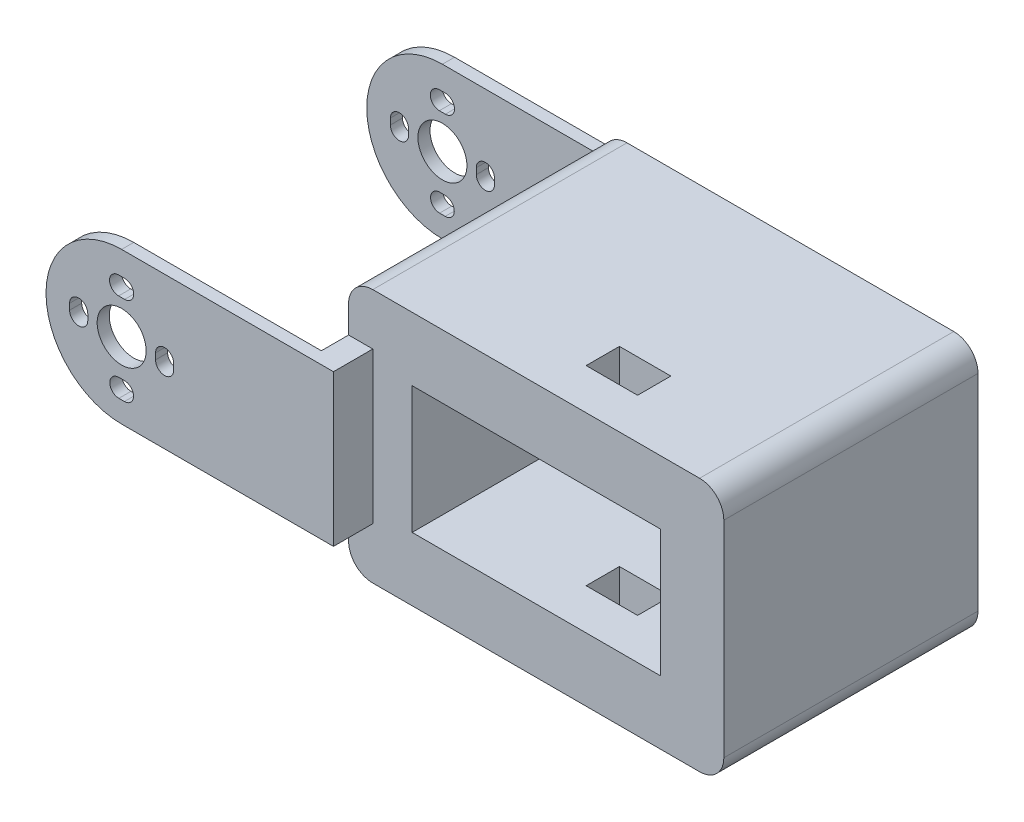
SolidWorks part; units mm, degrees
ref_plane "前基準面" through (0, 0, 0) normal (0, 0, 1) x (1, 0, 0)
ref_plane "上基準面" through (0, 0, 0) normal (0, 1, 0) x (1, 0, 0)
ref_plane "右基準面" through (0, 0, 0) normal (1, 0, 0) x (0, 0, -1)
sketch "Sketch1" plane through (0, 0, 0) normal (0, 0, 1) x (1, 0, 0)
  line L0 (-29.0958, -4.1361) -> (32.9042, -4.1361) construction
  line L1 (-18.5958, 6.3639) -> (22.4042, 6.3639)
  line L2 (-18.5958, 6.3639) -> (-18.5958, -14.6361)
  line L3 (-18.5958, -14.6361) -> (22.4042, -14.6361)
  line L4 (22.4042, 6.3639) -> (22.4042, -14.6361)
  line L5 (-29.0958, 16.8639) -> (32.9042, 16.8639)
  line L6 (-29.0958, 16.8639) -> (-29.0958, -25.1361)
  line L7 (-29.0958, -25.1361) -> (32.9042, -25.1361)
  line L8 (32.9042, 16.8639) -> (32.9042, -25.1361)
  line L9 (1.9042, 16.8639) -> (1.9042, -25.1361) construction
  line L10 (22.4042, -4.1361) -> (-18.5958, -4.1361) construction
  line L11 (1.9042, 6.3639) -> (1.9042, -14.6361) construction
  point P16 (1.9042, -4.1361)
  point P17 (1.9042, -4.1361)
  dimension "D1" = 21
  dimension "D2" = 41
  dimension "D3" = 62
  dimension "D4" = 42
extrude "Boss-Extrude1" add sketch "Sketch1" along normal blind 42
sketch "Sketch2" plane through (0, 0, 42) normal (0, 0, 1) x (1, 0, 0)
  line L0 (-18.5958, -4.1361) -> (-29.0958, -4.1361) construction
  line L1 (-25.0958, -4.1361) -> (-29.0958, -4.1361) construction
  line L3 (-29.0958, 16.8639) -> (-29.0958, -25.1361) construction
  line L4 (-18.5958, 6.3639) -> (-18.5958, -14.6361) construction
  line L5 (-29.0958, 8.3639) -> (-25.0958, 8.3639)
  line L6 (-29.0958, 8.3639) -> (-29.0958, -16.6361)
  line L7 (-29.0958, -16.6361) -> (-25.0958, -16.6361)
  line L8 (-25.0958, 8.3639) -> (-25.0958, -16.6361)
  dimension "D1" = 25
  dimension "D2" = 4
extrude "Boss-Extrude2" add sketch "Sketch2" along normal blind 4.5
extrude "Boss-Extrude3" add sketch "Sketch2<2>" against normal blind 45.55
sketch "Sketch2<2>" plane through (0, 0, 42) normal (0, 0, 1) x (1, 0, 0) same geometry as "Sketch2"
sketch "Sketch3" plane through (0, 0, 46.5) normal (0, 0, 1) x (1, 0, 0)
  line L0 (-60.5958, 2.9639) -> (-59.5958, 2.9639) construction
  line L1 (-25.0958, 8.3639) -> (-60.0958, 8.3639)
  line L2 (-25.0958, 8.3639) -> (-25.0958, -16.6361)
  line L3 (-25.0958, -16.6361) -> (-60.0958, -16.6361)
  line L4 (-60.0958, 8.3639) -> (-60.0958, -16.6361)
  line L5 (-60.5958, 4.4639) -> (-59.5958, 4.4639)
  line L6 (-60.5958, 1.4639) -> (-59.5958, 1.4639)
  line L7 (-60.0958, 8.3639) -> (-60.0958, -16.6361) construction
  line L8 (-60.5559, -11.6762) -> (-59.6357, -11.6762) construction
  line L9 (-60.5559, -10.1762) -> (-59.6357, -10.1762)
  line L10 (-60.5559, -13.1762) -> (-59.6357, -13.1762)
  line L11 (-60.0958, -4.1361) -> (-72.5958, -4.1361) construction
  line L12 (-67.1958, -3.6361) -> (-67.1958, -4.6361) construction
  line L15 (-65.6958, -3.6361) -> (-65.6958, -4.6361)
  line L16 (-68.6958, -3.6361) -> (-68.6958, -4.6361)
  line L17 (-52.9958, -3.6361) -> (-52.9958, -4.6361) construction
  line L18 (-51.4958, -3.6361) -> (-51.4958, -4.6361)
  line L19 (-54.4958, -3.6361) -> (-54.4958, -4.6361)
  line L20 (-60.0958, -4.1361) -> (-25.0958, -4.1361) construction
  line L21 (-29.0958, 8.3639) -> (-29.0958, -16.6361) construction
  arc A0 (-60.0958, 8.3639) -> (-60.0958, -16.6361) centre (-60.0958, -4.1361) ccw
  circle A1 centre (-60.0958, -4.1361) radius 4.05
  arc A3 (-60.5958, 4.4639) -> (-60.5958, 1.4639) centre (-60.5958, 2.9639) ccw
  arc A4 (-59.5958, 1.4639) -> (-59.5958, 4.4639) centre (-59.5958, 2.9639) ccw
  arc A5 (-60.5559, -10.1762) -> (-60.5559, -13.1762) centre (-60.5559, -11.6762) ccw
  arc A6 (-59.6357, -13.1762) -> (-59.6357, -10.1762) centre (-59.6357, -11.6762) ccw
  arc A9 (-65.6958, -3.6361) -> (-68.6958, -3.6361) centre (-67.1958, -3.6361) ccw
  arc A10 (-68.6958, -4.6361) -> (-65.6958, -4.6361) centre (-67.1958, -4.6361) ccw
  arc A11 (-51.4958, -3.6361) -> (-54.4958, -3.6361) centre (-52.9958, -3.6361) ccw
  arc A12 (-54.4958, -4.6361) -> (-51.4958, -4.6361) centre (-52.9958, -4.6361) ccw
  point P9 (-60.0958, 2.9639)
  point P14 (-58.0958, 2.9639)
  point P15 (-62.0958, 2.9639)
  point P19 (-60.0958, -11.6762)
  point P25 (-67.1958, -4.1361)
  point P31 (-67.1958, -2.1361)
  point P32 (-67.1958, -6.1361)
  point P34 (-65.6958, -4.1361)
  point P37 (-52.9958, -4.1361)
  point P42 (-52.9958, -2.1361)
  point P43 (-52.9958, -6.1361)
  line M15 (-29.0958, 8.3639) -> (-29.0958, -16.6361)
  line M16 (-29.0958, -16.6361) -> (-25.0958, -16.6361)
  line M17 (-25.0958, -16.6361) -> (-25.0958, 8.3639)
  line M18 (-25.0958, 8.3639) -> (-29.0958, 8.3639)
  dimension "D2" = 4
  dimension "D10" = 5.6
  dimension "D9" = 4
  dimension "D3" = 3
  dimension "D4" = 5.6
  dimension "D5" = 25
  dimension "D6" = 6.0402
  dimension "D7" = 0
  dimension "D8" = 3
  dimension "D11" = 5.6
  dimension "D12" = 3
  dimension "D13" = 4
  dimension "D14" = 31
extrude "Boss-Extrude6" add sketch "Sketch3" along normal blind 2 contours A5 L9 L4 A1 L6 A3 L5 A0 L10 A10 L16 A9 L15 | A6 L10 L4 L3 L1 L5 A4 L6 A1 L9 A12 L19 A11 L18 M15 | M18 M15 M16 M17 region at (-27.0958, -4.1361, 46.5) region at (-43.7932, -4.1343, 46.5) region at (-60.3753, 6.4139, 46.5)
extrude "Boss-Extrude7" add sketch "Sketch3<8>" against normal blind 53 contours A5 L9 L4 A1 L6 A3 L5 A0 L10 A10 L16 A9 L15 | A6 L10 L4 L3 L1 L5 A4 L6 A1 L9 A12 L19 A11 L18 M15 | M18 M15 M16 M17 region at (-27.0958, -4.1361, 46.5) region at (-43.7932, -4.1343, 46.5) region at (-60.3753, 6.4139, 46.5)
sketch "Sketch3<8>" plane through (0, 0, 46.5) normal (0, 0, 1) x (1, 0, 0) same geometry as "Sketch3"
extrude "Cut-Extrude1" cut sketch "Sketch3<11>" against normal blind 51 contours A6 L10 L4 L3 L1 L5 A4 L6 A1 L9 A12 L19 A11 L18 M15 | A5 L9 L4 A1 L6 A3 L5 A0 L10 A10 L16 A9 L15 region at (-43.7932, -4.1343, 46.5) region at (-60.3753, 6.4139, 46.5)
sketch "Sketch3<11>" plane through (0, 0, 46.5) normal (0, 0, 1) x (1, 0, 0) same geometry as "Sketch3"
sketch "草圖1" plane through (0, 16.8639, 0) normal (0, 1, 0) x (1, 0, 0)
  line L1 (11.9042, -35.25) -> (3.4042, -35.25)
  line L2 (11.9042, -35.25) -> (11.9042, -29.75)
  line L3 (11.9042, -29.75) -> (3.4042, -29.75)
  line L4 (3.4042, -35.25) -> (3.4042, -29.75)
  line L5 (32.9042, -42) -> (-29.0958, -42) construction
  line L7 (22.4042, -42) -> (22.4042, 0) construction
  dimension "D1" = 8.5
  dimension "D2" = 5.5
  dimension "D3" = 10.5
  dimension "D4" = 6.75
extrude "除料-伸長1" cut sketch "草圖1" against normal blind 42
fillet "圓角3" radius 4 1 edges at (-29.0958, 16.8639, 21) type face fillet first side face at (7.6542, 16.8639, 32.5) second side face at (-29.0958, -4.1361, 21)
fillet "圓角4" radius 4 1 edges at (32.9042, 16.8639, 21) type face fillet first side face at (7.6542, 16.8639, 32.5) second side face at (32.9042, -4.1361, 21)
fillet "圓角5" radius 4 1 edges at (32.9042, -25.1361, 21) type face fillet first side face at (7.6542, -25.1361, 32.5) second side face at (32.9042, -6.1361, 21)
fillet "圓角6" radius 4 1 edges at (-29.0958, -25.1361, 21) type face fillet first side face at (7.6542, -25.1361, 32.5) second side face at (-29.0958, -4.8027, 21)
